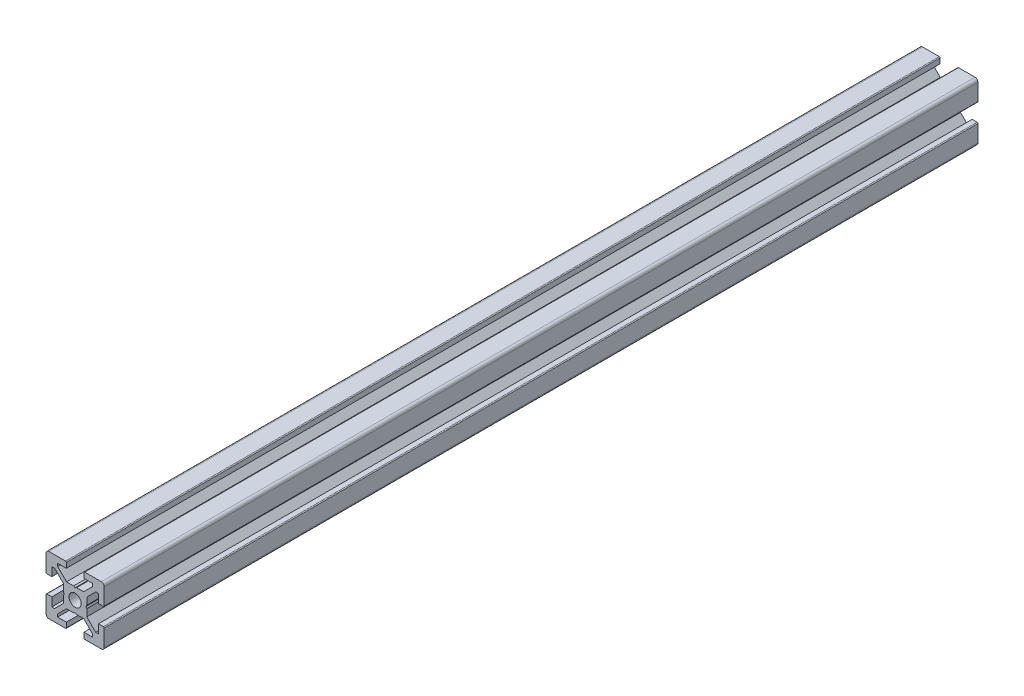
SolidWorks part; units mm, degrees
material "6063-T5"
ref_plane "Front Plane" through (0, 0, 0) normal (0, 0, 1) x (1, 0, 0)
ref_plane "Top Plane" through (0, 0, 0) normal (0, 1, 0) x (1, 0, 0)
ref_plane "Right Plane" through (0, 0, 0) normal (1, 0, 0) x (0, 0, -1)
ref_plane "Plane1" through (0, 0, 0) normal (0, 0, 1) x (1, 0, 0)
sketch "Sketch1" plane through (0, 0, 0) normal (0, 0, 1) x (1, 0, 0)
  line L0 (-10, 9) -> (-10, 3.3)
  line L1 (-9.7, 3) -> (-8, 3)
  line L2 (-8, 3) -> (-8, 6)
  line L3 (-8, 6) -> (-7.0607, 6)
  line L4 (-7.0607, 6) -> (-4, 2.9393)
  line L5 (-4, 2.9393) -> (-4, 0.5196)
  line L6 (-4, 0.5196) -> (-3.7, 0)
  line L7 (-3.7, 0) -> (-4, -0.5196)
  line L8 (-4, -0.5196) -> (-4, -2.9393)
  line L9 (-4, -2.9393) -> (-7.0607, -6)
  line L10 (-7.0607, -6) -> (-8, -6)
  line L11 (-8, -6) -> (-8, -3)
  line L12 (-8, -3) -> (-9.7, -3)
  line L13 (-10, -3.3) -> (-10, -9)
  line L14 (-9, -10) -> (-3.3, -10)
  line L15 (-3, -9.7) -> (-3, -8)
  line L16 (-3, -8) -> (-6, -8)
  line L17 (-6, -8) -> (-6, -7.0607)
  line L18 (-6, -7.0607) -> (-2.9393, -4)
  line L19 (-2.9393, -4) -> (-0.5196, -4)
  line L20 (-0.5196, -4) -> (0, -3.7)
  line L21 (0, -3.7) -> (0.5196, -4)
  line L22 (0.5196, -4) -> (2.9393, -4)
  line L23 (2.9393, -4) -> (6, -7.0607)
  line L24 (6, -7.0607) -> (6, -8)
  line L25 (6, -8) -> (3, -8)
  line L26 (3, -8) -> (3, -9.7)
  line L27 (3.3, -10) -> (9, -10)
  line L28 (10, -9) -> (10, -3.3)
  line L29 (9.7, -3) -> (8, -3)
  line L30 (8, -3) -> (8, -6)
  line L31 (8, -6) -> (7.0606, -6)
  line L32 (7.0606, -6) -> (4, -2.9393)
  line L33 (4, -2.9393) -> (4, -0.5196)
  line L34 (4, -0.5196) -> (3.7, 0)
  line L35 (3.7, 0) -> (4, 0.5196)
  line L36 (4, 0.5196) -> (4, 2.9393)
  line L37 (4, 2.9393) -> (7.0607, 6)
  line L38 (7.0607, 6) -> (8, 6)
  line L39 (8, 6) -> (8, 3)
  line L40 (8, 3) -> (9.7, 3)
  line L41 (10, 3.3) -> (10, 9)
  line L42 (9, 10) -> (3.3, 10)
  line L43 (3, 9.7) -> (3, 8)
  line L44 (3, 8) -> (6, 8)
  line L45 (6, 8) -> (6, 7.0607)
  line L46 (6, 7.0607) -> (2.9393, 4)
  line L47 (2.9393, 4) -> (0.5196, 4)
  line L48 (0.5196, 4) -> (0, 3.7)
  line L49 (0, 3.7) -> (-0.5196, 4)
  line L50 (-0.5196, 4) -> (-2.9394, 4)
  line L51 (-2.9394, 4) -> (-6, 7.0606)
  line L52 (-6, 7.0606) -> (-6, 8)
  line L53 (-6, 8) -> (-3, 8)
  line L54 (-3, 8) -> (-3, 9.7)
  line L55 (-3.3, 10) -> (-9, 10)
  arc A0 (-10, 3.3) -> (-9.7, 3) centre (-9.7, 3.3) ccw
  arc A1 (-9.7, -3) -> (-10, -3.3) centre (-9.7, -3.3) ccw
  arc A2 (-10, -9) -> (-9, -10) centre (-9, -9) ccw
  arc A3 (-3.3, -10) -> (-3, -9.7) centre (-3.3, -9.7) ccw
  arc A4 (3, -9.7) -> (3.3, -10) centre (3.3, -9.7) ccw
  arc A5 (9, -10) -> (10, -9) centre (9, -9) ccw
  arc A6 (10, -3.3) -> (9.7, -3) centre (9.7, -3.3) ccw
  arc A7 (9.7, 3) -> (10, 3.3) centre (9.7, 3.3) ccw
  arc A8 (10, 9) -> (9, 10) centre (9, 9) ccw
  arc A9 (3.3, 10) -> (3, 9.7) centre (3.3, 9.7) ccw
  arc A10 (-3, 9.7) -> (-3.3, 10) centre (-3.3, 9.7) ccw
  arc A11 (-9, 10) -> (-10, 9) centre (-9, 9) ccw
extrude "Boss-Extrude1" add sketch "Sketch1" against normal blind 300
ref_plane "Plane2" through (0, 0, 0) normal (1, 0, 0) x (0, 0, -1)
sketch "Sketch2" plane through (0, 0, 0) normal (1, 0, 0) x (0, 0, -1)
  line L0 (0, 0) -> (0, 2.1)
  line L1 (0, 2.1) -> (330, 2.1)
  line L2 (330, 2.1) -> (330, 0)
  line L3 (330, 0) -> (0, 0)
  line L4 (330, 0) -> (0, 0) construction
  dimension "D1" = 2.1
  dimension "D2" = 330
revolve "Cut-Revolve1" cut sketch "Sketch2" angle 360 about L4 reverse direction yes
ref_plane "Plane3" through (0, 0, -150) normal (0, 0, 1) x (1, 0, 0)
sketch "Sketch4" plane through (4, 0, 0) normal (1, 0, 0) x (0, 0, -1)
  line L0 (300, 0) -> (0, 0) construction
  line L1 (0, -2.9393) -> (0, -0.5196) construction
  line L2 (150, 2.9393) -> (150, -2.9393) construction
  line L3 (300, 2.9393) -> (0, 2.9393) construction
  line L4 (300, -2.9393) -> (0, -2.9393) construction
  circle A0 centre (10, 0) radius 2.5
  circle A1 centre (290, 0) radius 2.5
  dimension "D1" = 5
  dimension "D2" = 10
extrude "Cut-Extrude1" cut sketch "Sketch4" against normal up to surface (8 mm away) up to face at (-4, 1.7295, -150)
ref_axis "Axis1" through (0, 0, -300) along (0, 0, 1)
sketch "Sketch5" plane through (0, 4, 0) normal (0, 1, 0) x (1, 0, 0)
  line L0 (2.9393, 300) -> (0.5196, 300) construction
  line L1 (0, 300) -> (0, 0) construction
  line L2 (2.9393, 150) -> (-2.9394, 150) construction
  line L3 (2.9393, 300) -> (2.9393, 0) construction
  line L4 (-2.9394, 300) -> (-2.9394, 0) construction
  circle A0 centre (0, 290) radius 2.5
  circle A1 centre (0, 10) radius 2.5
  dimension "D1" = 5
  dimension "D2" = 10
extrude "Cut-Extrude2" cut sketch "Sketch5" against normal up to surface (8 mm away) up to face at (-1.7295, -4, -150)
sketch "Sketch6" plane through (0, 4, 0) normal (0, 1, 0) x (1, 0, 0)
  circle A0 centre (0, 220) radius 2.1 construction
  circle A1 centre (0, 220) radius 2.1 construction
  circle A2 centre (0, 220) radius 2.5
  dimension "D1" = 5
extrude "Cut-Extrude3" [suppressed] cut sketch "Sketch6" against normal up to surface (8 mm away) contours A2
